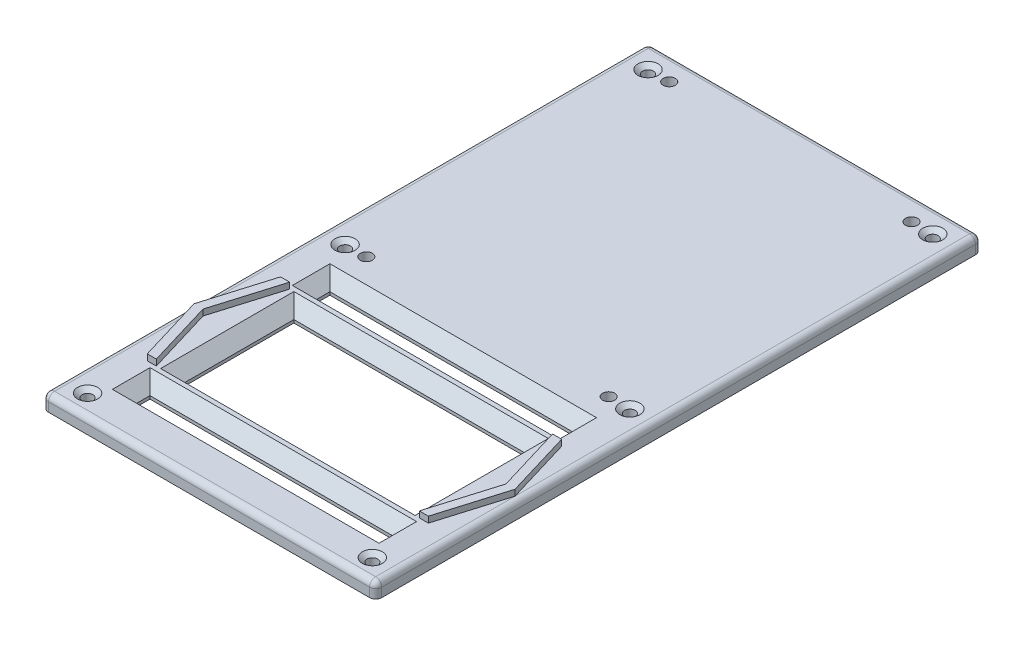
SolidWorks part; units mm, degrees
ref_plane "Front Plane" through (0, 0, 0) normal (0, 0, 1) x (1, 0, 0)
ref_plane "Top Plane" through (0, 0, 0) normal (0, 1, 0) x (1, 0, 0)
ref_plane "Right Plane" through (0, 0, 0) normal (1, 0, 0) x (0, 0, -1)
sketch "Sketch1" plane through (0, 0, 0) normal (0, 1, 0) x (1, 0, 0)
  line L1 (-69.85, -25.4) -> (69.85, -25.4)
  line L2 (-69.85, -25.4) -> (-69.85, 228.6)
  line L3 (-69.85, 228.6) -> (69.85, 228.6)
  line L4 (69.85, -25.4) -> (69.85, 228.6)
  line L5 (0, 228.6) -> (0, -25.4) construction
  line L6 (-69.85, 101.6) -> (69.85, 101.6) construction
  point P0 (0, 101.6)
  dimension "D1" = 254
  dimension "D2" = 139.7
  dimension "D3" = 101.6
extrude "Boss-Extrude1" add sketch "Sketch1" along normal blind 6.35
sketch "Sketch2" plane through (0, 6.35, 0) normal (0, 1, 0) x (1, 0, 0)
  line L0 (-69.85, -25.4) -> (69.85, -25.4) construction
  line L1 (-48.26, 12.7) -> (48.26, 12.7)
  line L2 (-48.26, 12.7) -> (-48.26, 58.42)
  line L3 (-48.26, 58.42) -> (48.26, 58.42)
  line L4 (48.26, 12.7) -> (48.26, 58.42)
  line L5 (0, 58.42) -> (0, 12.7) construction
  line L6 (-48.26, 35.56) -> (48.26, 35.56) construction
  point P0 (0, 35.56)
  dimension "D1" = 45.72
  dimension "D2" = 96.52
  dimension "D3" = 38.1
extrude "Main Hole" cut sketch "Sketch2" against normal through all
ref_plane "Plane1" through (0, 0, -35.56) normal (0, 0, 1) x (1, 0, 0)
sketch "Sketch3" plane through (0, 6.35, 0) normal (0, 1, 0) x (1, 0, 0)
  line L0 (48.26, 58.42) -> (-48.26, 58.42) construction
  line L1 (-50.8, 70.485) -> (50.8, 70.485)
  line L2 (-50.8, 70.485) -> (-50.8, 76.073)
  line L3 (-50.8, 76.073) -> (50.8, 76.073)
  line L4 (50.8, 70.485) -> (50.8, 76.073)
  point P4 (0, 70.485)
  dimension "D1" = 101.6
  dimension "D2" = 5.588
  dimension "D3" = 12.065
extrude "NeoPixel" cut sketch "Sketch3" against normal through all
mirror "Mirror2" about plane through (0, 0, -35.56) normal (0, 0, 1) of "NeoPixel"
sketch "Sketch5" plane through (0, 0, 0) normal (0, -1, 0) x (1, 0, 0)
  line L0 (69.85, -228.6) -> (-69.85, -228.6) construction
  line L1 (67.31, -226.06) -> (-67.31, -226.06)
  line L2 (67.31, -226.06) -> (67.31, 22.86)
  line L3 (67.31, 22.86) -> (-67.31, 22.86)
  line L4 (-67.31, -226.06) -> (-67.31, 22.86)
  line L5 (64.77, -223.52) -> (-64.77, -223.52)
  line L6 (64.77, -223.52) -> (64.77, 20.32)
  line L7 (64.77, 20.32) -> (-64.77, 20.32)
  line L8 (-64.77, -223.52) -> (-64.77, 20.32)
  line L9 (-69.85, -228.6) -> (-69.85, 25.4) construction
  line L10 (-69.85, 25.4) -> (69.85, 25.4) construction
  line L11 (69.85, 25.4) -> (69.85, -228.6) construction
  dimension "D1" = 2.54
  dimension "D2" = 2.54
  dimension "D3" = 2.54
  dimension "D4" = 2.54
  dimension "D5" = 2.54
  dimension "D6" = 2.54
  dimension "D7" = 2.54
  dimension "D8" = 2.54
extrude "Boss-Extrude2" [suppressed] add sketch "Sketch5" along normal blind 2.54 contours L4 L1 L2 L3 L5 L8 L7 L6
chamfer "Chamfer1" distance 5.08 angle 45 8 edges at (50.8, 6.35, 2.159) (0, 6.35, 4.953) (-50.8, 6.35, 2.159) (0, 6.35, -0.635) (-50.8, 6.35, -73.279) (0, 6.35, -70.485) (50.8, 6.35, -73.279) (0, 6.35, -76.073)
chamfer "Chamfer2" distance 5.08 angle 45 4 edges at (48.26, 6.35, -35.56) (0, 6.35, -12.7) (-48.26, 6.35, -35.56) (0, 6.35, -58.42)
sketch "Sketch6" plane through (0, 0, 0) normal (0, -1, 0) x (1, 0, 0)
  line L0 (0.6985, -35.56) -> (-0.6985, -35.56) construction
  line L1 (50.8, -10.16) -> (-50.8, -10.16)
  line L2 (50.8, -10.16) -> (50.8, -60.96)
  line L3 (50.8, -60.96) -> (-50.8, -60.96)
  line L4 (-50.8, -10.16) -> (-50.8, -60.96)
  line L5 (0, -60.96) -> (0, -10.16) construction
  line L6 (50.8, -35.56) -> (-50.8, -35.56) construction
  line L7 (0, -4.8895) -> (0, 4.8895) construction
  line L8 (6.35, -63.5) -> (6.35, -60.96)
  line L9 (53.34, -7.62) -> (-53.34, -7.62)
  line L10 (53.34, -7.62) -> (53.34, -63.5)
  line L11 (53.34, -63.5) -> (-53.34, -63.5)
  line L12 (-53.34, -7.62) -> (-53.34, -63.5)
  line L13 (0, -63.5) -> (0, -7.62) construction
  line L14 (53.34, -35.56) -> (-53.34, -35.56) construction
  line L31 (-6.35, -63.5) -> (-6.35, -60.96)
  line L32 (6.35, -62.23) -> (-6.35, -62.23) construction
  point P0 (0, -35.56)
  point P8 (0, -35.56)
  point P16 (0, -62.23)
  dimension "D1" = 2.54
  dimension "D2" = 2.54
  dimension "D3" = 50.8
  dimension "D4" = 101.6
  dimension "D5" = 12.7
extrude "Boss-Extrude3" [suppressed] add sketch "Sketch6" along normal blind 4.064 contours L9 L12 L11 L10 L4 L1 L2 L3
sketch "Sketch7" plane through (0, 6.35, 0) normal (0, 1, 0) x (1, 0, 0)
  line L0 (-50.8, 91.313) -> (50.8, 91.313) construction
  line L1 (0, -4.8895) -> (0, 4.8895) construction
  line L2 (-55.88, 81.153) -> (55.88, 81.153) construction
  circle A0 centre (50.8, 91.313) radius 2.54
  circle A1 centre (-50.8, 91.313) radius 2.54
  circle A2 centre (-50.8, 218.313) radius 2.54
  circle A3 centre (50.8, 218.313) radius 2.54
  point P4 (0, 91.313)
  dimension "D1" = 5.08
  dimension "D3" = 10.16
  dimension "D5" = 127
  dimension "D2" = 101.6
  dimension "D4" = 2
extrude "Cut-Extrude1" cut sketch "Sketch7" against normal up to next
sketch "Sketch8" plane through (0, 6.35, 0) normal (0, 1, 0) x (1, 0, 0)
  line L0 (58.928, 63.5) -> (67.31, 35.56)
  line L1 (67.31, 35.56) -> (58.928, 7.62)
  line L2 (58.928, 7.62) -> (55.118, 7.62)
  line L3 (55.118, 7.62) -> (63.5, 35.56)
  line L4 (63.5, 35.56) -> (55.118, 63.5)
  line L5 (55.118, 63.5) -> (58.928, 63.5)
  line L6 (63.5, 35.56) -> (67.31, 35.56) construction
  line L7 (-53.34, 63.5) -> (53.34, 63.5) construction
  line L8 (-0.6985, 35.56) -> (0.6985, 35.56) construction
  line L9 (53.34, 7.62) -> (-53.34, 7.62) construction
  dimension "D1" = 3.81
  dimension "D2" = 8.382
  dimension "D3" = 1.778
extrude "Boss-Extrude4" add sketch "Sketch8" along normal blind 2.54
mirror "Mirror3" about plane through (0, 0, 0) normal (1, 0, 0) of "Boss-Extrude4"
hole_wizard "Front-Back Mounting HOles" positions "Sketch9" profile "Sketch10" countersink size "#8" standard "ANSI Inch" end condition through all
sketch "Sketch9" plane through (0, 6.35, 0) normal (0, 1, 0) x (1, 0, 0)
  line L0 (69.85, -25.4) -> (69.85, 228.6) construction
  line L1 (-69.85, 228.6) -> (-69.85, -25.4) construction
  line L2 (69.85, 228.6) -> (-69.85, 228.6) construction
  point P0 (59.69, 218.313)
  point P2 (-59.69, 218.313)
  point P4 (-59.69, 91.313)
  point P6 (59.69, 91.313)
  point P8 (59.69, -16.637)
  point P10 (-59.69, -16.637)
  dimension "D5" = 10.287
  dimension "D1" = 10.16
  dimension "D2" = 10.16
  dimension "D3" = 107.95
  dimension "D4" = 127
sketch "Sketch10" plane through (59.69, 6.35, -218.313) normal (1, 0, 0) x (0, 0, 1)
  line L0 (0, 0) -> (0, 6.35)
  line L1 (0, 6.35) -> (2.2479, 6.35)
  line L2 (2.2479, 6.35) -> (2.2479, 1.6518)
  line L3 (2.2479, 1.6518) -> (4.2164, 0)
  line L5 (4.2164, 0) -> (0, 0)
  line L6 (-2.2479, 1.6518) -> (-4.2164, 0) construction
  line L11 (0, -6.35) -> (0, 107.95) construction
  dimension "Thru Hole Dia." = 4.4958
  dimension "Thru Hole Depth" = 6.35
  dimension "Near C'Sink Dia." = 8.4328
  dimension "Near C'Sink Angle" = 100
fillet "Corner Fillet" radius 2.54 4 edges at (-69.85, 3.175, -228.6) (69.85, 3.175, -228.6) (-69.85, 3.175, 25.4) (69.85, 3.175, 25.4)
fillet "Fillet2" radius 2.54 8 edges at (-69.1061, 6.35, -227.8561) (0, 6.35, -228.6) (69.1061, 6.35, -227.8561) (69.85, 6.35, -101.6) (69.1061, 6.35, 24.6561) (0, 6.35, 25.4) (-69.1061, 6.35, 24.6561) (-69.85, 6.35, -101.6)
equation "\"D1@Sketch2\"=1.8in"
equation "\"D2@Sketch2\"=3.8in"
